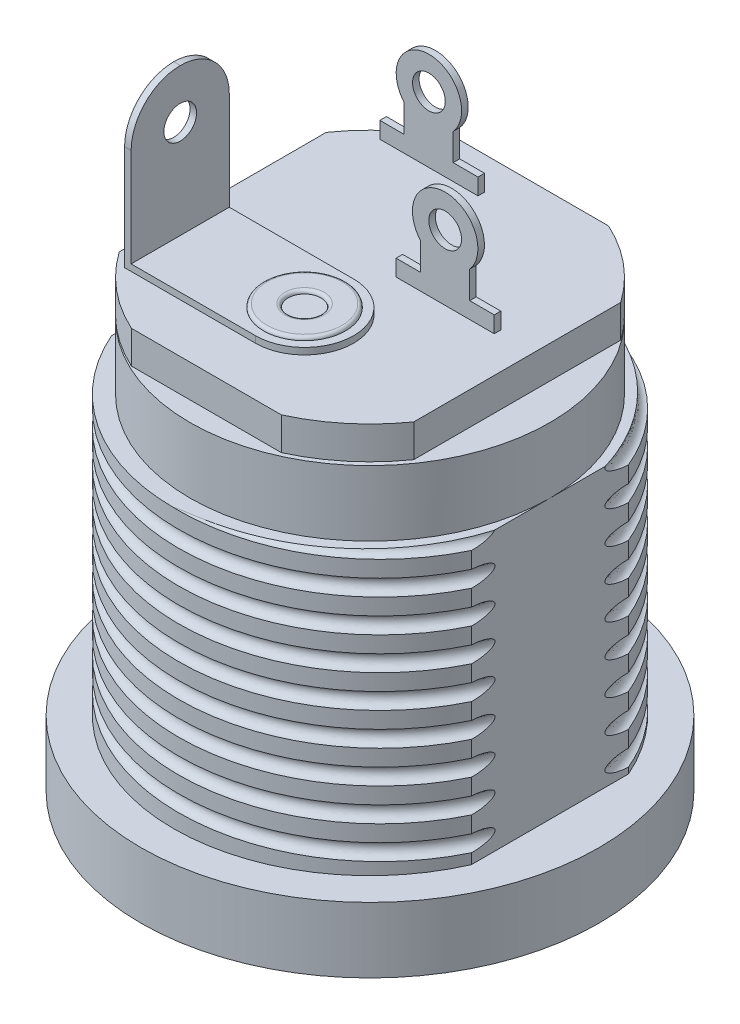
SolidWorks part; units mm, degrees
ref_plane "Front Plane" through (0, 0, 0) normal (0, 0, 1) x (1, 0, 0)
ref_plane "Top Plane" through (0, 0, 0) normal (0, 1, 0) x (1, 0, 0)
ref_plane "Right Plane" through (0, 0, 0) normal (1, 0, 0) x (0, 0, -1)
sketch "Sketch1" plane through (0, 0, 0) normal (0, 1, 0) x (1, 0, 0)
  circle A0 centre (0, 0) radius 7
  dimension "D1" = 14
extrude "Boss-Extrude1" add sketch "Sketch1" along normal blind 2
sketch "Sketch3" plane through (0, 2, 0) normal (0, 1, 0) x (1, 0, 0)
  circle A0 centre (0, 0) radius 6
  dimension "D1" = 12
extrude "Boss-Extrude2" add sketch "Sketch3" along normal blind 10.5
sketch "Sketch4" plane through (0, 12.5, 0) normal (0, 1, 0) x (1, 0, 0)
  line L1 (-5.5, -9.5536) -> (5.5, -9.5536)
  line L2 (-5.5, -9.5536) -> (-5.5, 9.5536)
  line L3 (-5.5, 9.5536) -> (5.5, 9.5536)
  line L4 (5.5, -9.5536) -> (5.5, 9.5536)
  line L5 (-5.5, -9.5536) -> (5.5, 9.5536) construction
  line L6 (-5.5, 9.5536) -> (5.5, -9.5536) construction
  point P0 (0, 0)
  dimension "D1" = 11
extrude "Cut-Extrude1" cut sketch "Sketch4" against normal up to surface (10.5 mm away) flip side to cut up to face at (0, 2, 7)
sketch "Sketch5" plane through (0, 2, 0) normal (0, 1, 0) x (1, 0, 0)
  circle A0 centre (0, 0) radius 6
curve "Helix/Spiral1" pitch 1 height 9 turns 9
sketch "Sketch6" plane through (0, 0, 0) normal (0, 0, 1) x (1, 0, 0)
  line L0 (7, 2) -> (-7, 2) construction
  circle A0 centre (-6, 2) radius 0.25
  spline S0 degree 3 poles (-6, 2) (-6, 2.0207) (-5.6876, 2.0626) (-4.3531, 2.125) (-2.3559, 2.1875) (0, 2.25) (2.3559, 2.3125) (4.3531, 2.375) (5.6876, 2.4375) (6.1562, 2.5) (5.6876, 2.5625) (4.3531, 2.625) (2.3559, 2.6875) (0, 2.75) (-2.3559, 2.8125) (-4.3531, 2.875) (-5.6876, 2.9375) (-6.1562, 3) (-5.6876, 3.0625) (-4.3531, 3.125) (-2.3559, 3.1875) (0, 3.25) (2.3559, 3.3125) (4.3531, 3.375) (5.6876, 3.4375) (6.1562, 3.5) (5.6876, 3.5625) (4.3531, 3.625) (2.3559, 3.6875) (0, 3.75) (-2.3559, 3.8125) (-4.3531, 3.875) (-5.6876, 3.9375) (-6.1562, 4) (-5.6876, 4.0625) (-4.3531, 4.125) (-2.3559, 4.1875) (0, 4.25) (2.3559, 4.3125) (4.3531, 4.375) (5.6876, 4.4375) (6.1562, 4.5) (5.6876, 4.5625) (4.3531, 4.625) (2.3559, 4.6875) (0, 4.75) (-2.3559, 4.8125) (-4.3531, 4.875) (-5.6876, 4.9375) (-6.1562, 5) (-5.6876, 5.0625) (-4.3531, 5.125) (-2.3559, 5.1875) (0, 5.25) (2.3559, 5.3125) (4.3531, 5.375) (5.6876, 5.4375) (6.1562, 5.5) (5.6876, 5.5625) (4.3531, 5.625) (2.3559, 5.6875) (0, 5.75) (-2.3559, 5.8125) (-4.3531, 5.875) (-5.6876, 5.9375) (-6.1562, 6) (-5.6876, 6.0625) (-4.3531, 6.125) (-2.3559, 6.1875) (0, 6.25) (2.3559, 6.3125) (4.3531, 6.375) (5.6876, 6.4375) (6.1562, 6.5) (5.6876, 6.5625) (4.3531, 6.625) (2.3559, 6.6875) (0, 6.75) (-2.3559, 6.8125) (-4.3531, 6.875) (-5.6876, 6.9375) (-6.1562, 7) (-5.6876, 7.0625) (-4.3531, 7.125) (-2.3559, 7.1875) (0, 7.25) (2.3559, 7.3125) (4.3531, 7.375) (5.6876, 7.4375) (6.1562, 7.5) (5.6876, 7.5625) (4.3531, 7.625) (2.3559, 7.6875) (0, 7.75) (-2.3559, 7.8125) (-4.3531, 7.875) (-5.6876, 7.9375) (-6.1562, 8) (-5.6876, 8.0625) (-4.3531, 8.125) (-2.3559, 8.1875) (0, 8.25) (2.3559, 8.3125) (4.3531, 8.375) (5.6876, 8.4375) (6.1562, 8.5) (5.6876, 8.5625) (4.3531, 8.625) (2.3559, 8.6875) (0, 8.75) (-2.3559, 8.8125) (-4.3531, 8.875) (-5.6876, 8.9375) (-6.1562, 9) (-5.6876, 9.0625) (-4.3531, 9.125) (-2.3559, 9.1875) (0, 9.25) (2.3559, 9.3125) (4.3531, 9.375) (5.6876, 9.4375) (6.1562, 9.5) (5.6876, 9.5625) (4.3531, 9.625) (2.3559, 9.6875) (0, 9.75) (-2.3559, 9.8125) (-4.3531, 9.875) (-5.6876, 9.9375) (-6.1562, 10) (-5.6876, 10.0625) (-4.3531, 10.125) (-2.3559, 10.1875) (0, 10.25) (2.3559, 10.3125) (4.3531, 10.375) (5.6876, 10.4375) (6.1562, 10.5) (5.6876, 10.5625) (4.3531, 10.625) (2.3559, 10.6875) (0, 10.75) (-2.3559, 10.8125) (-4.3531, 10.875) (-5.6876, 10.9374) (-6, 10.9793) (-6, 11) knots 0 0 0 0 0.006944 0.013889 0.020833 0.027778 0.034722 0.041667 0.048611 0.055556 0.0625 0.069444 0.076389 0.083333 0.090278 0.097222 0.104167 0.111111 0.118056 0.125 0.131944 0.138889 0.145833 0.152778 0.159722 0.166667 0.173611 0.180556 0.1875 0.194444 0.201389 0.208333 0.215278 0.222222 0.229167 0.236111 0.243056 0.25 0.256944 0.263889 0.270833 0.277778 0.284722 0.291667 0.298611 0.305556 0.3125 0.319444 0.326389 0.333333 0.340278 0.347222 0.354167 0.361111 0.368056 0.375 0.381944 0.388889 0.395833 0.402778 0.409722 0.416667 0.423611 0.430556 0.4375 0.444444 0.451389 0.458333 0.465278 0.472222 0.479167 0.486111 0.493056 0.5 0.506944 0.513889 0.520833 0.527778 0.534722 0.541667 0.548611 0.555556 0.5625 0.569444 0.576389 0.583333 0.590278 0.597222 0.604167 0.611111 0.618056 0.625 0.631944 0.638889 0.645833 0.652778 0.659722 0.666667 0.673611 0.680556 0.6875 0.694444 0.701389 0.708333 0.715278 0.722222 0.729167 0.736111 0.743056 0.75 0.756944 0.763889 0.770833 0.777778 0.784722 0.791667 0.798611 0.805556 0.8125 0.819444 0.826389 0.833333 0.840278 0.847222 0.854167 0.861111 0.868056 0.875 0.881944 0.888889 0.895833 0.902778 0.909722 0.916667 0.923611 0.930556 0.9375 0.944444 0.951389 0.958333 0.965278 0.972222 0.979167 0.986111 0.993056 1 1 1 1 construction
  dimension "D1" = 0.5
sweep "Cut-Sweep1" cut profiles "Sketch6" path "Helix/Spiral1"
sketch "Sketch7" plane through (0, 12.5, 0) normal (0, 1, 0) x (1, 0, 0)
  circle A0 centre (0, 0) radius 5.5
  dimension "D1" = 11
extrude "Cut-Extrude2" cut sketch "Sketch7" against normal blind 2 flip side to cut
sketch "Sketch8" plane through (0, 12.5, 0) normal (0, 1, 0) x (1, 0, 0)
  line L1 (-2.2913, -5) -> (2.2913, -5)
  line L2 (-4.5, -3.1623) -> (-4.5, 3.1623)
  line L3 (-2.2913, 5) -> (2.2913, 5)
  line L4 (4.5, -3.1623) -> (4.5, 3.1623)
  line L5 (-3.6793, -4.0881) -> (3.6793, 4.0881) construction
  line L6 (-3.6793, 4.0881) -> (3.6793, -4.0881) construction
  arc A0 (4.5, 3.1623) -> (2.2913, 5) centre (0, 0) ccw
  arc A2 (-4.5, -3.1623) -> (-2.2913, -5) centre (0, 0) ccw
  arc A3 (2.2913, -5) -> (4.5, -3.1623) centre (0, 0) ccw
  arc A4 (-2.2913, 5) -> (-4.5, 3.1623) centre (0, 0) ccw
extrude "Boss-Extrude3" add sketch "Sketch8" along normal blind 1 from offset 0.1
sketch "Sketch10" plane through (0, 13.6, 0) normal (0, 1, 0) x (1, 0, 0)
  line L0 (0, -7.48) -> (0, 7.48) construction
  line L1 (-2.2913, -5) -> (2.2913, -5) construction
  line L2 (0, -0.5) -> (-4, -0.5)
  line L3 (-4, -0.5) -> (-4, -3.5)
  line L4 (0, -3.5) -> (-4, -3.5)
  arc A0 (0, -3.5) -> (0, -0.5) centre (0, -2) ccw
  dimension "D1" = 3
  dimension "D2" = 3
  dimension "D3" = 4
extrude "Boss-Extrude4" add sketch "Sketch10" along normal blind 0.2
sketch "Sketch12" plane through (0, 13.8, 0) normal (0, 1, 0) x (1, 0, 0)
  line L0 (0, -0.5) -> (-4, -0.5) construction
  line L1 (-4, -0.5) -> (-3.8, -0.5)
  line L2 (-4, -0.5) -> (-4, -3.5)
  line L3 (-4, -3.5) -> (-3.8, -3.5)
  line L4 (-3.8, -0.5) -> (-3.8, -3.5)
  line L5 (-4, -0.5) -> (-4, -3.5) construction
  line L6 (-4, -3.5) -> (0, -3.5) construction
  dimension "D1" = 0.2
extrude "Boss-Extrude5" add sketch "Sketch12" along normal blind 4.5
fillet "Fillet1" radius 1.5 2 edges at (-3.9, 18.3, 0.5) (-3.9, 18.3, 3.5)
sketch "Sketch13" plane through (-4, 0, 0) normal (-1, 0, 0) x (0, 0, 1)
  circle A0 centre (2, 16.8) radius 0.5
  arc A2 (2, 18.3) -> (0.5, 16.8) centre (2, 16.8) ccw construction
  dimension "D1" = 1
extrude "Cut-Extrude3" cut sketch "Sketch13" against normal through all
sketch "Sketch14" plane through (0, 13.6, 0) normal (0, 1, 0) x (-1, 0, 0)
  line L0 (4.5, -3.1623) -> (4.5, 3.1623) construction
  line L1 (0.5, -3.8) -> (3.5, -3.8)
  line L2 (0.5, -3.8) -> (0.5, -4)
  line L3 (0.5, -4) -> (3.5, -4)
  line L4 (3.5, -3.8) -> (3.5, -4)
  line L5 (0.5, -3.8) -> (3.5, -4) construction
  line L6 (0.5, -4) -> (3.5, -3.8) construction
  line L7 (-2.2913, -5) -> (2.2913, -5) construction
  point P0 (2, -3.9)
  dimension "D1" = 0.2
  dimension "D2" = 1
  dimension "D3" = 1
  dimension "D4" = 3
extrude "Boss-Extrude6" add sketch "Sketch14" along normal blind 0.5
sketch "Sketch16" plane through (0, 0, -3.8) normal (0, 0, 1) x (1, 0, 0)
  line L0 (-2.7592, 14.1) -> (-1.2592, 14.1)
  line L2 (-1.2592, 14.9284) -> (-1.2592, 14.1)
  line L3 (-2.7592, 14.9492) -> (-2.7592, 14.1)
  line L4 (-1.9861, 16.6) -> (2.4967, 16.6) construction
  line L5 (4.5, 13.6) -> (2.2913, 13.6) construction
  line L6 (-3.5, 14.1) -> (-0.5, 14.1) construction
  line L7 (-2, 14.1) -> (-2, 17.0467) construction
  arc A0 (-1.2592, 14.9284) -> (-2.7592, 14.9492) centre (-2, 15.6001) ccw
  circle A1 centre (-2, 15.6001) radius 0.5
  dimension "D1" = 2
  dimension "D2" = 1
  dimension "D3" = 3
  dimension "D4" = 1.5
extrude "Boss-Extrude7" add sketch "Sketch16" against normal blind 0.2
sketch "Sketch17" plane through (0, 13.6, 0) normal (0, 1, 0) x (1, 0, 0)
  line L0 (-2.2913, -5) -> (2.2913, -5) construction
  line L1 (0.397, 0.4) -> (3.397, 0.4)
  line L2 (0.397, 0.4) -> (0.397, 0.6)
  line L3 (0.397, 0.6) -> (3.397, 0.6)
  line L4 (3.397, 0.4) -> (3.397, 0.6)
  line L5 (0.397, 0.4) -> (3.397, 0.6) construction
  line L6 (0.397, 0.6) -> (3.397, 0.4) construction
  point P0 (1.897, 0.5)
  dimension "D1" = 5.5
  dimension "D2" = 0.2
  dimension "D3" = 3
extrude "Boss-Extrude8" add sketch "Sketch17" along normal blind 0.5
sketch "Sketch18" plane through (0, 0, -0.4) normal (0, 0, 1) x (1, 0, 0)
  line L0 (1.147, 14.1) -> (2.647, 14.1)
  line L2 (1.897, 16.6) -> (0.3475, 16.6) construction
  line L3 (4.5, 13.6) -> (2.2913, 13.6) construction
  line L4 (2.647, 14.9386) -> (2.647, 14.1)
  line L5 (1.147, 14.9386) -> (1.147, 14.1)
  arc A0 (2.647, 14.9386) -> (1.147, 14.9386) centre (1.897, 15.6) ccw
  circle A1 centre (1.897, 15.6) radius 0.5
  dimension "D1" = 2
  dimension "D2" = 1
  dimension "D3" = 3
extrude "Boss-Extrude9" add sketch "Sketch18" against normal blind 0.2
sketch "Sketch21" plane through (0, 0, 0) normal (0, -1, 0) x (1, 0, 0)
  line L0 (0, -7.7) -> (0, 7.7) construction
  line L1 (0, -7) -> (5.2109, -7) construction
  line L2 (0, -5) -> (6.3434, -5) construction
  circle A0 centre (0, -2) radius 3
  circle A1 centre (0, 0) radius 7 construction
  dimension "D1" = 6
  dimension "D2" = 2
extrude "Cut-Extrude4" cut sketch "Sketch21" against normal blind 10
sketch "Sketch22" plane through (0, 10, 0) normal (0, -1, 0) x (1, 0, 0)
  circle A0 centre (0, -2) radius 1
  dimension "D1" = 2
extrude "Boss-Extrude10" add sketch "Sketch22" along normal blind 8
fillet "Fillet2" radius 1 1 edges at (0, 2, -3)
sketch "Sketch23" plane through (0, 0, 0) normal (0, -1, 0) x (1, 0, 0)
  text T0 "MX" font "Century Gothic" height in points 8
extrude "Boss-Extrude11" add sketch "Sketch23" along normal blind 0.1
sketch "Sketch24" plane through (0, 13.8, 0) normal (0, 1, 0) x (1, 0, 0)
  circle A0 centre (0, -2) radius 1.25
  dimension "D1" = 2.5
extrude "Extrude-Thin1" add sketch "Sketch24" along normal blind 0.1 thin thin type one direction reverse wall 0.75
fillet "Fillet3" radius 0.1 2 edges at (0.5, 13.9, 2) (0, 13.9, 3.25)
